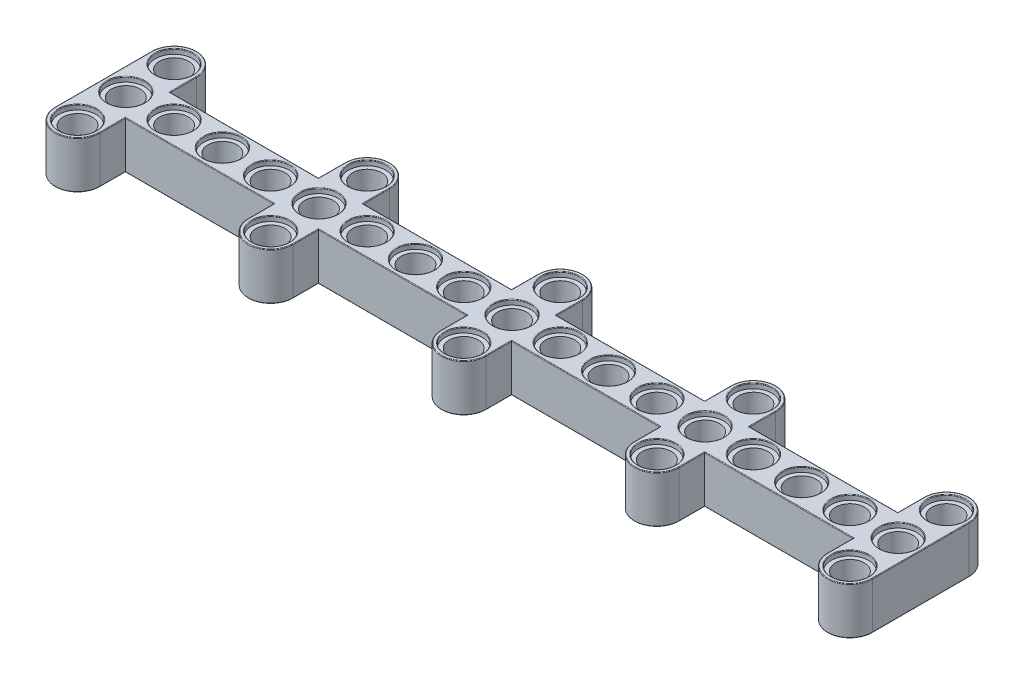
SolidWorks part; units mm, degrees
ref_plane "Ön Düzlem" through (0, 0, 0) normal (0, 0, 1) x (1, 0, 0)
ref_plane "Üst Düzlem" through (0, 0, 0) normal (0, 1, 0) x (1, 0, 0)
ref_plane "Sağ Düzlem" through (0, 0, 0) normal (1, 0, 0) x (0, 0, -1)
sketch "Çizim1" plane through (0, 0, 0) normal (0, 0, 1) x (1, 0, 0)
  line L1 (-3.7, -3.9) -> (3.7, -3.9)
  line L2 (-3.7, -3.9) -> (-3.7, 3.9)
  line L3 (-3.7, 3.9) -> (3.7, 3.9)
  line L4 (3.7, -3.9) -> (3.7, 3.9)
  line L5 (-3.7, -3.9) -> (3.7, 3.9) construction
  line L6 (-3.7, 3.9) -> (3.7, -3.9) construction
  point P0 (0, 0)
extrude "Yükseklik-Ekstrüzyon1" add sketch "Çizim1" along normal blind 23.4
sketch "Çizim2" plane through (0, 3.9, 0) normal (0, 1, 0) x (1, 0, 0)
  circle A0 centre (0, -11.7) radius 2.4
  circle A1 centre (0, -3.7) radius 2.4
  circle A2 centre (0, -19.7) radius 2.4
  dimension "D1" = 2
  dimension "D2" = 2
extrude "Kes-Ekstrüzyon1" cut sketch "Çizim2" against normal up to surface (7.8 mm away) up to face at (0, -3.9, 11.7)
fillet "Radyus1" 2 edges at (3.7, 0, 23.4) (-3.7, 0, 23.4) type full round first side face at (3.7, 0, 11.7) second side face at (-3.7, 0, 11.7) middle face at (0, 0, 23.4)
fillet "Radyus2" 2 edges at (-3.7, 0, 0) (3.7, 0, 0) type full round first side face at (-3.7, 0, 9.85) second side face at (3.7, 0, 9.85) middle face at (0, 0, 0)
sketch "Çizim3" plane through (0, 3.9, 0) normal (0, 1, 0) x (1, 0, 0)
  circle A0 centre (0, -3.7) radius 3.1
  circle A1 centre (0, -11.7) radius 3.1
  circle A2 centre (0, -19.7) radius 3.1
  dimension "D1" = 3
extrude "Kes-Ekstrüzyon2" cut sketch "Çizim3" against normal blind 0.8
sketch "Çizim4" plane through (0, -3.9, 0) normal (0, -1, 0) x (-1, 0, 0)
  circle A0 centre (0, -3.7) radius 3.1
  circle A1 centre (0, -11.7) radius 3.1
  circle A2 centre (0, -19.7) radius 3.1
  dimension "D1" = 3
extrude "Kes-Ekstrüzyon3" cut sketch "Çizim4" against normal blind 0.8
sketch "Çizim5" plane through (3.7, 0, 0) normal (1, 0, 0) x (0, 0, -1)
  line L0 (-19.7, 3.9) -> (-3.7, 3.9) construction
  line L1 (-15.47, -3.9) -> (-8.07, -3.9)
  line L2 (-15.47, -3.9) -> (-15.47, 3.9)
  line L3 (-15.47, 3.9) -> (-8.07, 3.9)
  line L4 (-8.07, -3.9) -> (-8.07, 3.9)
  line L5 (-15.47, -3.9) -> (-8.07, 3.9) construction
  line L6 (-15.47, 3.9) -> (-8.07, -3.9) construction
  point P0 (-11.77, 0)
extrude "Yükseklik-Ekstrüzyon2" add sketch "Çizim5" along normal blind 128
sketch "Çizim6" plane through (0, 3.9, 0) normal (0, 1, 0) x (1, 0, 0)
  circle A0 centre (8, -11.7) radius 2.4
  circle A2 centre (0, -11.7) radius 2.4 construction
  circle A3 centre (16, -11.7) radius 2.4
  circle A4 centre (24, -11.7) radius 2.4
  circle A5 centre (32, -11.7) radius 2.4
  circle A6 centre (40, -11.7) radius 2.4
  circle A7 centre (48, -11.7) radius 2.4
  circle A8 centre (56, -11.7) radius 2.4
  circle A9 centre (64, -11.7) radius 2.4
  circle A10 centre (72, -11.7) radius 2.4
  circle A11 centre (80, -11.7) radius 2.4
  circle A12 centre (88, -11.7) radius 2.4
  circle A13 centre (96, -11.7) radius 2.4
  circle A14 centre (104, -11.7) radius 2.4
  circle A15 centre (112, -11.7) radius 2.4
  dimension "D1" = 8
  dimension "D2" = 14
extrude "Kes-Ekstrüzyon4" cut sketch "Çizim6" against normal up to surface (7.8 mm away) up to face at (0, -3.9, 0.6)
sketch "Çizim7" plane through (0, 3.9, 0) normal (0, 1, 0) x (1, 0, 0)
  circle A0 centre (8, -11.7) radius 3.1
  circle A1 centre (16, -11.7) radius 3.1
  circle A2 centre (24, -11.7) radius 3.1
  circle A3 centre (32, -11.7) radius 3.1
  circle A4 centre (40, -11.7) radius 3.1
  circle A5 centre (48, -11.7) radius 3.1
  circle A6 centre (56, -11.7) radius 3.1
  circle A7 centre (64, -11.7) radius 3.1
  circle A8 centre (72, -11.7) radius 3.1
  circle A9 centre (80, -11.7) radius 3.1
  circle A10 centre (88, -11.7) radius 3.1
  circle A11 centre (96, -11.7) radius 3.1
  circle A12 centre (104, -11.7) radius 3.1
  circle A13 centre (112, -11.7) radius 3.1
  dimension "D1" = 14
extrude "Kes-Ekstrüzyon5" cut sketch "Çizim7" against normal blind 0.8
mirror "Aynalama1" about plane through (0, 0, 0) normal (0, 1, 0) of "Kes-Ekstrüzyon5"
sketch "Çizim8" plane through (0, -3.9, 0) normal (0, -1, 0) x (1, 0, 0)
  line L0 (0, 0) -> (169.5723, 0) construction
  line L1 (0, 23.4) -> (169.5723, 23.4) construction
  line L2 (0, 19.7) -> (171.7716, 19.7) construction
  line L3 (0, 3.7) -> (171.7716, 3.7) construction
  line L4 (32, 11.7) -> (32, 37.3095) construction
  line L5 (32, 11.7) -> (32, -13.4711) construction
  line L6 (64, 11.7) -> (64, 37.3095) construction
  line L7 (64, 11.7) -> (64, -14.1441) construction
  line L8 (0, -23.8816) -> (0, 45.6656) construction
  line L9 (96, 11.7) -> (96, 43.7004) construction
  line L10 (96, 11.7) -> (96, -21.7637) construction
  line L17 (35.7, 0) -> (28.3, 0)
  line L18 (35.7, 0) -> (35.7, 23.4)
  line L19 (35.7, 23.4) -> (28.3, 23.4)
  line L20 (28.3, 0) -> (28.3, 23.4)
  line L21 (35.7, 0) -> (28.3, 23.4) construction
  line L22 (35.7, 23.4) -> (28.3, 0) construction
  arc A0 (3.7, 19.7) -> (-3.7, 19.7) centre (0, 19.7) ccw construction
  dimension "D1" = 7.4
extrude "Yükseklik-Ekstrüzyon3" add sketch "Çizim8" against normal up to surface (7.8 mm away) up to face at (8, 3.9, 14.8)
sketch "Çizim11" plane through (0, -3.9, 0) normal (0, -1, 0) x (1, 0, 0)
  line L0 (60.3, 23.4) -> (60.3, 0)
  line L5 (28.3, 23.4) -> (35.7, 23.4)
  line L6 (28.3, 23.4) -> (28.3, 0)
  line L7 (28.3, 0) -> (35.7, 0)
  line L8 (35.7, 23.4) -> (35.7, 0)
  line L9 (60.3, 23.4) -> (67.7, 23.4)
  line L10 (67.7, 23.4) -> (67.7, 0)
  line L11 (60.3, 0) -> (67.7, 0)
  line L12 (92.3, 23.4) -> (92.3, 0)
  line L13 (92.3, 23.4) -> (99.7, 23.4)
  line L14 (99.7, 23.4) -> (99.7, 0)
  line L15 (92.3, 0) -> (99.7, 0)
  line L16 (124.3, 23.4) -> (124.3, 0)
  line L17 (124.3, 23.4) -> (131.7, 23.4)
  line L18 (131.7, 23.4) -> (131.7, 0)
  line L19 (124.3, 0) -> (131.7, 0)
  dimension "D1" = 4
extrude "Yükseklik-Ekstrüzyon5" add sketch "Çizim11" against normal up to surface (7.8 mm away) up to face at (40, 3.9, 14.8)
sketch "Çizim12" plane through (0, 3.9, 0) normal (0, 1, 0) x (1, 0, 0)
  line L0 (16, -11.7) -> (16, -78.3232) construction
  line L1 (0, -3.7) -> (32, -3.7) construction
  line L2 (0, -19.7) -> (32, -19.7) construction
  circle A0 centre (32, -3.7) radius 2.4
  circle A2 centre (32, -19.7) radius 2.4
  circle A3 centre (64, -19.7) radius 2.4
  circle A4 centre (32, -11.7) radius 2.4
  circle A5 centre (64, -3.7) radius 2.4
  circle A6 centre (96, -19.7) radius 2.4
  circle A7 centre (64, -11.7) radius 2.4
  circle A8 centre (96, -3.7) radius 2.4
  circle A9 centre (128, -19.7) radius 2.4
  circle A10 centre (96, -11.7) radius 2.4
  circle A11 centre (128, -3.7) radius 2.4
  circle A13 centre (128, -11.7) radius 2.4
  dimension "D1" = 4
  dimension "D2" = 4
extrude "Kes-Ekstrüzyon6" cut sketch "Çizim12" against normal up to surface (7.8 mm away) up to face at (40, -3.9, 14.8)
sketch "Çizim13" plane through (0, 3.9, 0) normal (0, 1, 0) x (1, 0, 0)
  circle A0 centre (32, -3.7) radius 3.1
  circle A1 centre (32, -11.7) radius 3.1
  circle A2 centre (32, -19.7) radius 3.1
  circle A3 centre (64, -11.7) radius 3.1
  circle A4 centre (64, -19.7) radius 3.1
  circle A5 centre (64, -3.7) radius 3.1
  circle A6 centre (96, -11.7) radius 3.1
  circle A7 centre (96, -19.7) radius 3.1
  circle A8 centre (96, -3.7) radius 3.1
  circle A9 centre (128, -11.7) radius 3.1
  circle A10 centre (128, -19.7) radius 3.1
  circle A11 centre (128, -3.7) radius 3.1
  dimension "D1" = 3
  dimension "D2" = 4
extrude "Kes-Ekstrüzyon7" cut sketch "Çizim13" against normal blind 0.8
mirror "Aynalama2" about plane through (0, 0, 0) normal (0, 1, 0) of "Kes-Ekstrüzyon7"
fillet "Radyus3" 2 edges at (28.3, 0, 0) (35.7, 0, 0) type full round first side face at (28.3, 0, 4.035) second side face at (35.7, 0, 4.035) middle face at (32, 0, 0)
fillet "Radyus4" 2 edges at (28.3, 0, 23.4) (35.7, 0, 23.4) type full round first side face at (28.3, 0, 19.435) second side face at (35.7, 0, 19.435) middle face at (32, 0, 23.4)
fillet "Radyus5" 2 edges at (60.3, 0, 0) (67.7, 0, 0) type full round first side face at (60.3, 0, 4.035) second side face at (67.7, 0, 4.035) middle face at (64, 0, 0)
fillet "Radyus6" 2 edges at (67.7, 0, 23.4) (60.3, 0, 23.4) type full round first side face at (67.7, 0, 19.435) second side face at (60.3, 0, 19.435) middle face at (64, 0, 23.4)
fillet "Radyus7" 2 edges at (92.3, 0, 23.4) (99.7, 0, 23.4) type full round first side face at (92.3, 0, 19.435) second side face at (99.7, 0, 19.435) middle face at (96, 0, 23.4)
fillet "Radyus8" 2 edges at (92.3, 0, 0) (99.7, 0, 0) type full round first side face at (92.3, 0, 4.035) second side face at (99.7, 0, 4.035) middle face at (96, 0, 0)
fillet "Radyus9" 2 edges at (124.3, 0, 23.4) (131.7, 0, 23.4) type full round first side face at (124.3, 0, 19.435) second side face at (131.7, 0, 11.7) middle face at (128, 0, 23.4)
fillet "Radyus10" 2 edges at (124.3, 0, 0) (131.7, 0, 0) type full round first side face at (124.3, 0, 4.035) second side face at (131.7, 0, 9.85) middle face at (128, 0, 0)
sketch "Çizim15" plane through (0, 3.9, 0) normal (0, 1, 0) x (1, 0, 0)
  line L0 (128, -11.7) -> (112, -11.7) construction
  circle A0 centre (120, -11.7) radius 2.4
extrude "Kes-Ekstrüzyon8" cut sketch "Çizim15" against normal up to surface (7.8 mm away) up to face at (128, -3.9, 22.8)
sketch "Çizim16" plane through (0, 3.9, 0) normal (0, 1, 0) x (1, 0, 0)
  circle A0 centre (120, -11.7) radius 3.1
extrude "Kes-Ekstrüzyon9" cut sketch "Çizim16" against normal blind 0.8
mirror "Aynalama3" about plane through (0, 0, 0) normal (0, 1, 0) of "Kes-Ekstrüzyon9"
fillet "Radyus11" radius 0.1 63 edges at (112, -3.9, 14.8) (104, -3.9, 14.8) (72, -3.9, 14.8) (80, -3.9, 14.8) (88, -3.9, 14.8) (0, -3.9, 16.6) (0, -3.9, 8.6) (0, -3.9, 0.6) (24, -3.9, 14.8) (16, -3.9, 14.8) (8, -3.9, 14.8) (112, -3.9, 8.07) (99.7, -3.9, 5.885) (96, -3.9, 0) (92.3, -3.9, 5.885) (80, -3.9, 8.07) (67.7, -3.9, 5.885) (64, -3.9, 0) (60.3, -3.9, 5.885) (48, -3.9, 8.07) (35.7, -3.9, 5.885) (32, -3.9, 0) (28.3, -3.9, 5.885) (16, -3.9, 8.07) (3.7, -3.9, 5.885) (0, -3.9, 0) (-3.7, -3.9, 11.7) (0, -3.9, 23.4) (3.7, -3.9, 17.585) (16, -3.9, 15.47) (28.3, -3.9, 17.585) (32, -3.9, 23.4) (35.7, -3.9, 17.585) (48, -3.9, 15.47) (60.3, -3.9, 17.585) (64, -3.9, 23.4) (67.7, -3.9, 17.585) (80, -3.9, 15.47) (92.3, -3.9, 17.585) (96, -3.9, 23.4) (99.7, -3.9, 17.585) (112, -3.9, 15.47) (124.3, -3.9, 17.585) (128, -3.9, 23.4) (131.7, -3.9, 11.7) (128, -3.9, 0) (124.3, -3.9, 5.885) (56, -3.9, 14.8) (48, -3.9, 14.8) (40, -3.9, 14.8) (32, -3.9, 6.8) (64, -3.9, 22.8) (96, -3.9, 6.8) (96, -3.9, 14.8) (96, -3.9, 22.8) (64, -3.9, 14.8) (64, -3.9, 6.8) (32, -3.9, 22.8) (32, -3.9, 14.8) (128, -3.9, 6.8) (128, -3.9, 14.8) (128, -3.9, 22.8) (120, -3.9, 14.8)
fillet "Radyus12" radius 0.1 63 edges at (112, 3.9, 14.8) (104, 3.9, 14.8) (72, 3.9, 14.8) (80, 3.9, 14.8) (88, 3.9, 14.8) (0, 3.9, 22.8) (0, 3.9, 14.8) (0, 3.9, 6.8) (24, 3.9, 14.8) (16, 3.9, 14.8) (8, 3.9, 14.8) (128, 3.9, 23.4) (124.3, 3.9, 17.585) (112, 3.9, 15.47) (99.7, 3.9, 17.585) (96, 3.9, 23.4) (92.3, 3.9, 17.585) (80, 3.9, 15.47) (67.7, 3.9, 17.585) (64, 3.9, 23.4) (60.3, 3.9, 17.585) (48, 3.9, 15.47) (35.7, 3.9, 17.585) (32, 3.9, 23.4) (28.3, 3.9, 17.585) (16, 3.9, 15.47) (3.7, 3.9, 17.585) (0, 3.9, 23.4) (-3.7, 3.9, 11.7) (0, 3.9, 0) (3.7, 3.9, 5.885) (16, 3.9, 8.07) (28.3, 3.9, 5.885) (32, 3.9, 0) (35.7, 3.9, 5.885) (48, 3.9, 8.07) (60.3, 3.9, 5.885) (64, 3.9, 0) (67.7, 3.9, 5.885) (80, 3.9, 8.07) (92.3, 3.9, 5.885) (96, 3.9, 0) (99.7, 3.9, 5.885) (112, 3.9, 8.07) (124.3, 3.9, 5.885) (128, 3.9, 0) (131.7, 3.9, 11.7) (56, 3.9, 14.8) (48, 3.9, 14.8) (40, 3.9, 14.8) (32, 3.9, 6.8) (64, 3.9, 22.8) (96, 3.9, 6.8) (96, 3.9, 14.8) (96, 3.9, 22.8) (64, 3.9, 14.8) (64, 3.9, 6.8) (32, 3.9, 22.8) (32, 3.9, 14.8) (128, 3.9, 6.8) (128, 3.9, 14.8) (128, 3.9, 22.8) (120, 3.9, 14.8)
